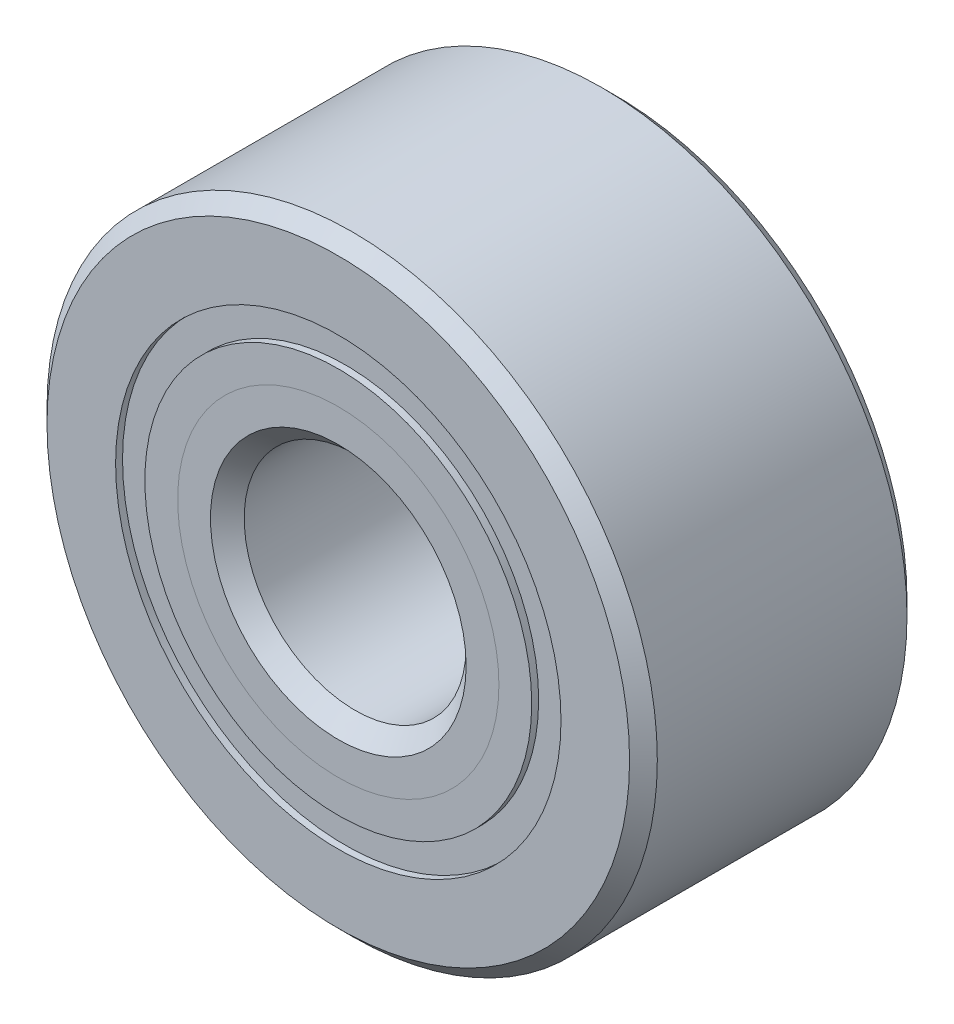
SolidWorks part; units mm, degrees
ref_plane "Front Plane" through (0, 0, 0) normal (0, 0, 1) x (1, 0, 0)
ref_plane "Top Plane" through (0, 0, 0) normal (0, 1, 0) x (1, 0, 0)
ref_plane "Right Plane" through (0, 0, 0) normal (1, 0, 0) x (0, 0, -1)
sketch "Sketch1" plane through (0, 0, 0) normal (1, 0, 0) x (0, 0, -1)
  line L0 (-3.9688, 0) -> (3.9688, 0) construction
  line L1 (0, 8.7312) -> (0, -8.7312) construction
  line L2 (3.5719, 8.7312) -> (-3.5719, 8.7312)
  line L3 (-3.5719, 8.7312) -> (-3.9688, 8.3344)
  line L4 (-3.9688, 8.3344) -> (-3.9688, 6.3718)
  line L5 (-3.9688, 6.3718) -> (-1.7639, 6.3718)
  line L6 (3.9688, 6.3718) -> (1.7639, 6.3718)
  line L7 (3.9688, 8.3344) -> (3.9688, 6.3718)
  line L8 (3.5719, 8.7312) -> (3.9688, 8.3344)
  line L9 (0, 8.7312) -> (0, 5.9531) construction
  line L10 (0, 5.9531) -> (0, 3.175) construction
  arc A0 (-1.7639, 6.3718) -> (1.7639, 6.3718) centre (0, 5.9531) cw
  point P14 (0, 3.175)
  dimension "D3" = 3.5278
  dimension "D1" = 45
  dimension "Width" = 7.9375
  dimension "OD" = 17.4625
  dimension "D2" = 0.3969
  dimension "Shaft Dia" = 6.35
  dimension "D4" = 0.4187
revolve "Revolve1" add sketch "Sketch1" angle 360 about L0
sketch "Sketch2" plane through (0, 0, 0) normal (1, 0, 0) x (0, 0, -1)
  line L0 (-3.9688, 5.5344) -> (-1.7639, 5.5344)
  line L1 (-3.9688, 8.3344) -> (-3.9688, -8.3344) construction
  line L2 (-3.9688, 5.5344) -> (-3.9688, 4.596)
  line L3 (-3.9688, 4.596) -> (-3.0303, 3.6576)
  line L4 (-3.0303, 3.6576) -> (0, 3.6576)
  line L5 (0, 8.7312) -> (0, -8.7312) construction
  line L6 (0, 3.6576) -> (0, 4.1402)
  line L7 (0, 4.1402) -> (0, 3.175) construction
  line L8 (-3.9688, 5.5344) -> (-3.9688, 3.6576) construction
  line L9 (-3.9688, 3.6576) -> (-3.0303, 3.6576) construction
  arc A0 (-1.7639, 5.5344) -> (0, 4.1402) centre (0, 5.9531) ccw
  arc A1 (1.7639, 6.3718) -> (-1.7639, 6.3718) centre (0, 5.9531) ccw construction
  circle A2 centre (0, 5.9531) radius 1.8129 construction
  dimension "D1" = 45
revolve "Revolve2" add sketch "Sketch2" angle 360 about L0
sketch "Sketch3" plane through (0, 0, 0) normal (1, 0, 0) x (0, 0, -1)
  line L0 (-3.9688, 4.596) -> (-3.0303, 3.6576)
  line L1 (-3.0303, 3.6576) -> (0, 3.6576)
  line L2 (0, 3.6576) -> (0, 4.1402)
  line L3 (-3.9688, 4.596) -> (-3.9688, 3.6576)
  line L4 (-3.9688, 5.5344) -> (-3.9688, 3.6576) construction
  line L5 (-3.9688, 3.6576) -> (-3.4861, 3.175)
  line L6 (-3.4861, 3.175) -> (3.5719, 3.175)
  line L7 (3.5719, 8.7312) -> (3.5719, -8.7312) construction
  line L8 (3.5719, 3.175) -> (3.9688, 3.5719)
  line L9 (3.9688, -8.3344) -> (3.9688, 8.3344) construction
  line L10 (3.9688, 3.5719) -> (3.9688, 5.5344)
  line L11 (3.9688, 5.5344) -> (1.7639, 5.5344)
  line L13 (3.5719, 8.7312) -> (3.9688, 8.3344) construction
  circle A0 centre (0, 5.9531) radius 1.8129 construction
  arc A1 (1.7639, 5.5344) -> (0, 4.1402) centre (0, 5.9531) cw
revolve "Revolve3" add sketch "Sketch3" angle 360 about L0
sketch "Sketch4" plane through (0, 0, 0) normal (1, 0, 0) x (0, 0, -1)
  line L0 (-1.8129, 5.9531) -> (1.8129, 5.9531)
  circle A1 centre (0, 5.9531) radius 1.8129 construction
  arc A2 (-1.8129, 5.9531) -> (1.8129, 5.9531) centre (0, 5.9531) cw
  arc A3 (1.7639, 6.3718) -> (-1.7639, 6.3718) centre (0, 5.9531) ccw construction
revolve "Revolve4" add sketch "Sketch4" angle 360 about L0
ref_axis "Axis1" through (0, 0, -3.9688) along (0, 0, 1)
pattern_circular "CirPattern1" count 8 every 45 about axis through (0, 0, -3.9688) along (0, 0, 1) of bodies 104
sketch "Sketch5" plane through (0, 0, 0) normal (1, 0, 0) x (0, 0, -1)
  line L0 (-3.9688, 6.3718) -> (-1.7639, 6.3718) construction
  line L1 (-3.7703, 6.3718) -> (-1.8129, 6.3718)
  line L2 (-3.7703, 6.3718) -> (-3.7703, 5.5344)
  line L3 (-3.7703, 5.5344) -> (-1.8129, 5.5344)
  line L4 (-1.8129, 6.3718) -> (-1.8129, 5.5344)
  line L5 (-3.9688, 5.5344) -> (-1.7639, 5.5344) construction
  line L6 (-3.5719, 8.7312) -> (-3.9688, 8.3344) construction
  line L7 (0, 8.7312) -> (0, 3.175) construction
  line L8 (3.7703, 5.5344) -> (1.8129, 5.5344)
  line L9 (1.8129, 6.3718) -> (1.8129, 5.5344)
  line L10 (3.7703, 6.3718) -> (1.8129, 6.3718)
  line L11 (3.7703, 6.3718) -> (3.7703, 5.5344)
  circle A0 centre (0, 5.9531) radius 1.8129 construction
  point P10 (-3.7703, 8.5328)
revolve "Revolve5" add sketch "Sketch5" angle 360 about L0
equation "\"D2@Sketch1\" = \"Width@Sketch1\"*.05"
equation "\"D3@Sketch1\" = \"Width@Sketch1\"/2.25"
equation "\"D4@Sketch1\" = (((\"OD@Sketch1\"-\"Width@Sketch1\")/2)/3.25)/3.5"
equation "\"D2@CirPattern1\" = 360/\"Balls@CirPattern1\""
